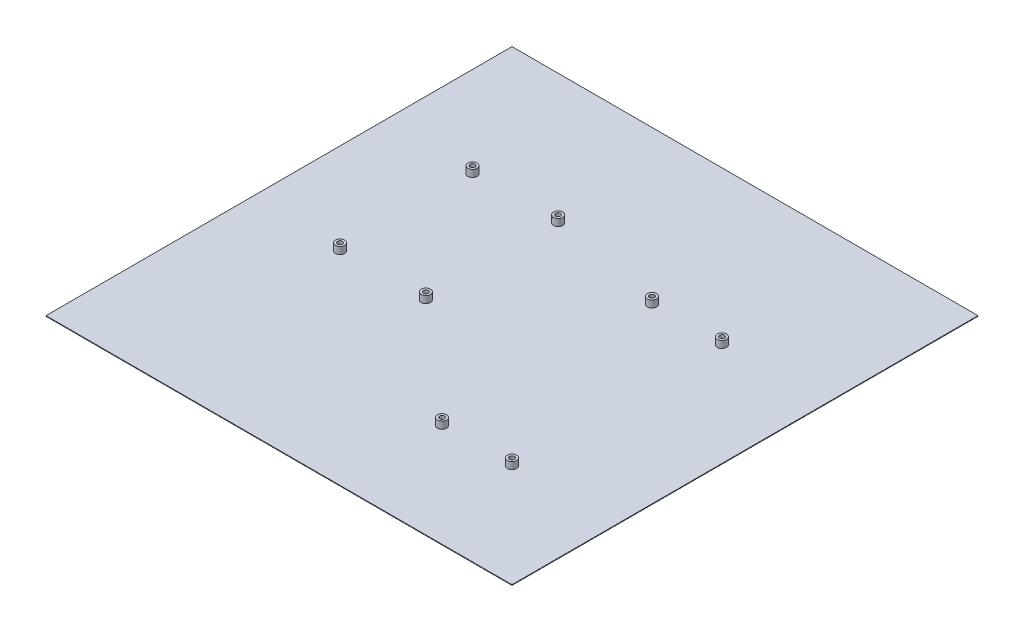
SolidWorks part; units mm, degrees
ref_plane "Front Plane" through (0, 0, 0) normal (0, 0, 1) x (1, 0, 0)
ref_plane "Top Plane" through (0, 0, 0) normal (0, 1, 0) x (1, 0, 0)
ref_plane "Right Plane" through (0, 0, 0) normal (1, 0, 0) x (0, 0, -1)
sketch "Sketch1" plane through (0, 0, 0) normal (0, 1, 0) x (1, 0, 0)
  line L1 (-166.5, -166.5) -> (166.5, -166.5)
  line L2 (-166.5, -166.5) -> (-166.5, 166.5)
  line L3 (-166.5, 166.5) -> (166.5, 166.5)
  line L4 (166.5, -166.5) -> (166.5, 166.5)
  line L5 (-166.5, -166.5) -> (166.5, 166.5) construction
  line L6 (-166.5, 166.5) -> (166.5, -166.5) construction
  point P0 (0, 0)
  dimension "D1" = 333
  dimension "D2" = 333
extrude "Boss-Extrude1" add sketch "Sketch1" along normal blind 0.45
sketch "Sketch6" plane through (0, 0.45, 0) normal (0, 1, 0) x (1, 0, 0)
  circle A0 centre (93, 57) radius 3.3
  circle A1 centre (43, 57) radius 3.3
  circle A2 centre (93, -93) radius 3.3
  circle A3 centre (43, -93) radius 3.3
  point P12 (0, 0)
  point P13 (0, 0)
  point P14 (0, 0)
  point P15 (0, 0)
  point P16 (93, -93)
  point P18 (43, -93)
  point P20 (93, 57)
  point P22 (43, 57)
sketch "Sketch7" plane through (0, 0.45, 0) normal (0, 1, 0) x (1, 0, 0)
  circle A0 centre (-101.9441, 73.7185) radius 3.3
  circle A1 centre (-40.9446, 73.9643) radius 3.3
  circle A2 centre (-40.5619, -21.035) radius 3.3
  circle A3 centre (-101.5614, -21.2807) radius 3.3
extrude "Boss-Extrude2" add sketch "Sketch7" along normal blind 5
sketch "Sketch8" plane through (0, 5.45, 0) normal (0, 1, 0) x (1, 0, 0)
  circle A0 centre (-40.5619, -21.035) radius 1.75
  circle A1 centre (-40.9446, 73.9643) radius 1.75
  circle A2 centre (-101.9441, 73.7185) radius 1.75
  circle A3 centre (-101.5614, -21.2807) radius 1.75
extrude "Cut-Extrude1" cut sketch "Sketch8" against normal blind 4
extrude "Boss-Extrude3" add sketch "Sketch6" along normal blind 5
sketch "Sketch10" plane through (0, 5.45, 0) normal (0, 1, 0) x (1, 0, 0)
  circle A0 centre (43, 57) radius 1.75
  circle A1 centre (93, 57) radius 1.75
  circle A2 centre (93, -93) radius 1.75
  circle A3 centre (43, -93) radius 1.75
extrude "Cut-Extrude2" cut sketch "Sketch10" against normal blind 4
